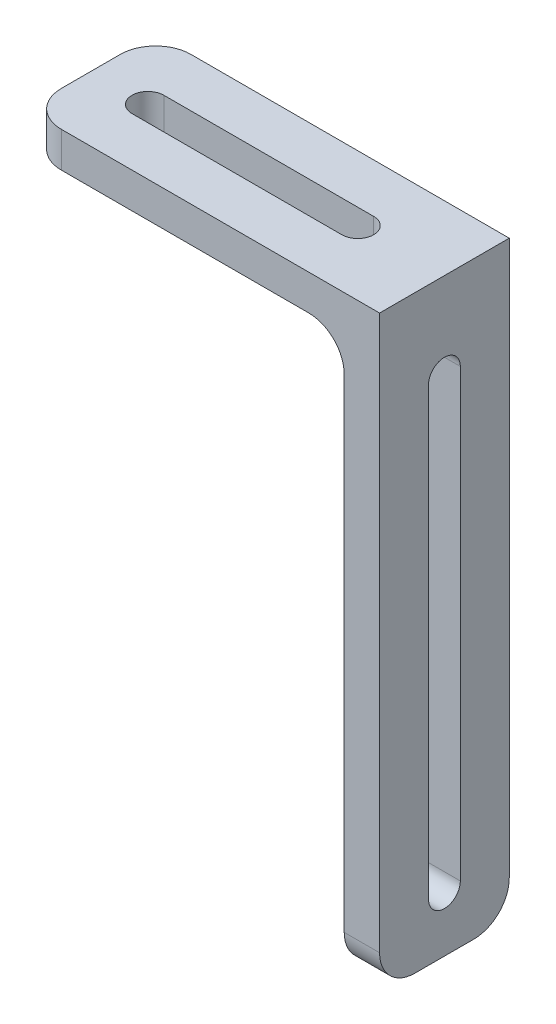
SolidWorks part; units mm, degrees
ref_plane "Front Plane" through (0, 0, 0) normal (0, 0, 1) x (1, 0, 0)
ref_plane "Top Plane" through (0, 0, 0) normal (0, 1, 0) x (1, 0, 0)
ref_plane "Right Plane" through (0, 0, 0) normal (1, 0, 0) x (0, 0, -1)
sketch "Sketch1" plane through (0, 0, 0) normal (0, 0, 1) x (1, 0, 0)
  line L0 (0, 0) -> (3, 0)
  line L1 (3, 0) -> (3, 50)
  line L2 (3, 50) -> (-27, 50)
  line L3 (-27, 50) -> (-27, 47)
  line L4 (-27, 47) -> (0, 47)
  line L5 (0, 47) -> (0, 0)
  dimension "D1" = 27
  dimension "D2" = 50
  dimension "D3" = 3
  dimension "D4" = 3
extrude "Boss-Extrude1" add sketch "Sketch1" along normal blind 11
sketch "Sketch6" plane through (3, 0, 0) normal (1, 0, 0) x (0, 0, -1)
  line L0 (-5.5, 50) -> (-5.5, 0) construction
  line L1 (-11, 50) -> (0, 50) construction
  line L2 (-11, 0) -> (0, 0) construction
  line L3 (-5.5, 42.65) -> (-5.5, 4.85) construction
  line L4 (-4.15, 42.65) -> (-4.15, 4.85)
  line L5 (-6.85, 42.65) -> (-6.85, 4.85)
  arc A0 (-4.15, 42.65) -> (-6.85, 42.65) centre (-5.5, 42.65) ccw
  arc A1 (-6.85, 4.85) -> (-4.15, 4.85) centre (-5.5, 4.85) ccw
  point P8 (-5.5, 23.75)
  point P13 (-5.5, 44)
  point P14 (-5.5, 3.5)
  dimension "D1" = 2.7
  dimension "D2" = 6
  dimension "D3" = 3.5
  dimension "D4" = 40.5
extrude "Cut-Extrude1" cut sketch "Sketch6" against normal through all
sketch "Sketch7" plane through (0, 50, 0) normal (0, 1, 0) x (1, 0, 0)
  line L0 (-27, -5.5) -> (3, -5.5) construction
  line L1 (-27, -11) -> (-27, 0) construction
  line L2 (3, -11) -> (3, 0) construction
  line L3 (-22.15, -5.5) -> (-4.35, -5.5) construction
  line L4 (-22.15, -4.15) -> (-4.35, -4.15)
  line L5 (-22.15, -6.85) -> (-4.35, -6.85)
  arc A0 (-22.15, -4.15) -> (-22.15, -6.85) centre (-22.15, -5.5) ccw
  arc A1 (-4.35, -6.85) -> (-4.35, -4.15) centre (-4.35, -5.5) ccw
  point P8 (-13.25, -5.5)
  point P13 (-23.5, -5.5)
  point P14 (-3, -5.5)
  dimension "D2" = 6
  dimension "D1" = 3.5
  dimension "D3" = 2.7
  dimension "D4" = 20.5
extrude "Cut-Extrude2" cut sketch "Sketch7" against normal through all contours L4 A1 L5 A0
fillet "Fillet1" radius 3 1 edges at (0, 47, 5.5)
fillet "Fillet2" radius 3 4 edges at (1.5, 0, 0) (1.5, 0, 11) (-27, 48.5, 11) (-27, 48.5, 0)
